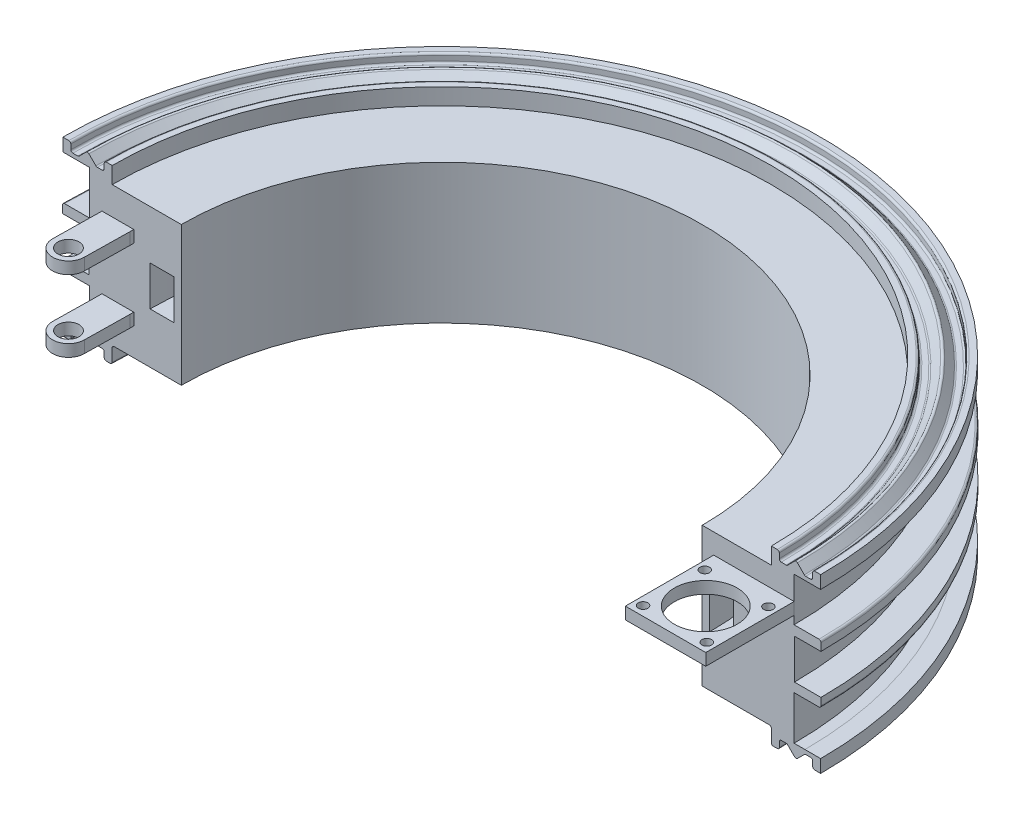
SolidWorks part; units mm, degrees
ref_plane "Front Plane" through (0, 0, 0) normal (0, 0, 1) x (1, 0, 0)
ref_plane "Top Plane" through (0, 0, 0) normal (0, 1, 0) x (1, 0, 0)
ref_plane "Right Plane" through (0, 0, 0) normal (1, 0, 0) x (0, 0, -1)
sketch "Sketch1" plane through (0, 0, 0) normal (0, 0, 1) x (1, 0, 0)
  line L0 (0, 21.2431) -> (0, -20.7935) construction
  line L1 (0, 21.2431) -> (0, -13.7569)
  line L12 (-23.1796, -1.3005) -> (-23.1796, 8.6995)
  line L14 (-29.847, 8.6995) -> (-29.847, 11.1239)
  line L23 (0, 3.7431) -> (-36.1577, 3.7431) construction
  line L25 (-7.8424, 8.9508) -> (-1.8424, 8.9508)
  line L26 (-7.8424, 8.9508) -> (-7.8424, -1.0492)
  line L27 (-7.8424, -1.0492) -> (-1.8424, -1.0492)
  line L28 (-1.8424, 8.9508) -> (-1.8424, -1.0492)
  line L29 (-21.3184, 23.1426) -> (-23.5684, 25.3926)
  line L30 (-23.5684, 25.3926) -> (-25.8184, 23.1426)
  line L32 (-25.8184, 22.1426) -> (-23.0909, 22.1426)
  line L33 (-23.0909, 22.1426) -> (-23.0909, 11.1239)
  line L34 (-23.0909, 11.1239) -> (-29.847, 11.1239)
  line L35 (-29.847, -3.6377) -> (-23.0909, -3.6377)
  line L42 (-29.847, -3.6377) -> (-29.847, -1.3005)
  line L43 (-29.847, -1.3005) -> (-23.1796, -1.3005)
  line L44 (-29.847, 8.6995) -> (-23.1796, 8.6995)
  line L45 (-21.3184, 23.1426) -> (-19.3684, 23.1426)
  line L46 (-19.3684, 23.1426) -> (-19.3684, 25.4025)
  line L47 (-17.3684, 25.4025) -> (-17.3684, 21.2431)
  line L48 (-17.3684, 21.2431) -> (0, 21.2431)
  line L49 (-19.3684, 25.4025) -> (-17.3684, 25.4025)
  line L50 (-25.8184, 23.1426) -> (-27.7684, 23.1426)
  line L51 (-27.7684, 23.1426) -> (-27.7684, 25.3862)
  line L52 (-27.7684, 25.3862) -> (-29.7684, 25.3862)
  line L53 (-29.7684, 25.3862) -> (-29.7684, 22.1426)
  line L54 (-29.7684, 22.1426) -> (-25.8184, 22.1426)
  line L65 (-29.7684, -14.6564) -> (-25.8184, -14.6564)
  line L66 (-29.7684, -17.9) -> (-29.7684, -14.6564)
  line L67 (-27.7684, -17.9) -> (-29.7684, -17.9)
  line L68 (-27.7684, -15.6564) -> (-27.7684, -17.9)
  line L69 (-25.8184, -15.6564) -> (-27.7684, -15.6564)
  line L70 (-19.3684, -17.9163) -> (-17.3684, -17.9163)
  line L71 (-17.3684, -13.7569) -> (0, -13.7569)
  line L72 (-17.3684, -17.9163) -> (-17.3684, -13.7569)
  line L73 (-19.3684, -15.6564) -> (-19.3684, -17.9163)
  line L74 (-21.3184, -15.6564) -> (-19.3684, -15.6564)
  line L75 (-23.0909, -14.6564) -> (-23.0909, -3.6377)
  line L76 (-25.8184, -14.6564) -> (-23.0909, -14.6564)
  line L77 (-23.5684, -17.9064) -> (-25.8184, -15.6564)
  line L78 (-21.3184, -15.6564) -> (-23.5684, -17.9064)
  line L79 (-29.847, 8.6995) -> (-29.847, -5.9646) construction
  line L80 (-23.5684, 25.3926) -> (-40.3715, 25.3926) construction
  line L81 (-40.3715, 25.3926) -> (-10.8825, 25.3926) construction
  line L82 (-23.0909, 11.1239) -> (-23.0909, -3.6377) construction
  dimension "D1" = 35
  dimension "D2" = 1.95
  dimension "D3" = 1
  dimension "D4" = 4.5
  dimension "D6" = 2
  dimension "D7" = 2
  dimension "D8" = 10
  dimension "D10" = 10
  dimension "D11" = 6
sketch "Sketch3" plane through (0, 0, 0) normal (0, 1, 0) x (1, 0, 0)
  arc A0 (0, 0) -> (130.92, 0) centre (65.46, 0) cw
sweep "Sweep3" add profiles "Sketch1" path "Sketch3"
sketch "Sketch13" plane through (0, 0, 0) normal (0, 0, 1) x (1, 0, 0)
  line L4 (-7.8424, 3.9508) -> (-7.8424, 18.9333) construction
  line L5 (-7.8424, -1.0492) -> (-7.8424, 8.9508) construction
  line L6 (-7.8424, 18.9333) -> (-7.8424, -5.0069) construction
  line L7 (-23.1796, 3.6995) -> (-1.1121, 3.6995) construction
  line L8 (-23.1796, 8.6995) -> (-23.1796, -1.3005) construction
  line L9 (-16.2449, 7.1426) -> (-16.2449, 2.1426) construction
  line L15 (-19.9387, -3.8005) -> (-11.9387, -3.8005)
  line L16 (-11.9387, -3.8005) -> (-11.9387, -6.8005)
  line L22 (-11.9387, -6.8005) -> (-19.9387, -6.8005)
  line L23 (-19.9387, -6.8005) -> (-19.9387, -3.8005)
  line L24 (-19.9387, 11.1995) -> (-11.9387, 11.1995)
  line L25 (-19.9387, 14.1995) -> (-19.9387, 11.1995)
  line L26 (-11.9387, 14.1995) -> (-19.9387, 14.1995)
  line L27 (-11.9387, 11.1995) -> (-11.9387, 14.1995)
  dimension "D1" = 3
  dimension "D2" = 8
  dimension "D3" = 7.5
ref_plane "Plane3" through (0, 3.6995, 0) normal (0, 1, 0) x (1, 0, 0)
sketch "Sketch17" plane through (0, 0, 0) normal (0, 0, 1) x (1, 0, 0)
  line L15 (154.0109, 16.1931) -> (133.8109, 16.1931)
  line L16 (154.0109, 22.1426) -> (154.0109, 11.1239) construction
  line L17 (133.8109, 16.1931) -> (133.8109, 13.1931)
  line L18 (133.8109, 13.1931) -> (154.0109, 13.1931)
  line L19 (154.0109, 13.1931) -> (154.0109, 16.1931)
  line L20 (130.92, 21.2431) -> (148.2883, 21.2431) construction
  dimension "D1" = 5.05
  dimension "D2" = 3
  dimension "D3" = 20.2
fillet "Fillet1" radius 0.5 1 edges at (65.46, 25.3926, -89.0284)
fillet "Fillet2" radius 0.5 1 edges at (65.46, 23.1426, -91.2784)
fillet "Fillet3" radius 0.5 1 edges at (65.46, 23.1426, -93.2284)
fillet "Fillet4" radius 0.5 2 edges at (65.46, 23.1426, -84.8284) (65.46, 23.1426, -86.7784)
fillet "Fillet5" radius 0.5 3 edges at (65.46, -17.9163, -84.8284) (65.46, -15.6564, -86.7784) (65.46, -17.9064, -89.0284)
fillet "Fillet6" radius 0.5 3 edges at (65.46, -13.7569, -82.8284) (65.46, -17.9163, -82.8284) (65.46, -15.6564, -84.8284)
fillet "Fillet7" radius 0.5 3 edges at (65.46, -15.6564, -91.2784) (65.46, -17.9, -93.2284) (65.46, -15.6564, -93.2284)
fillet "Fillet9" radius 0.5 2 edges at (65.46, -3.6377, -95.3069) (65.46, 11.1239, -95.3069)
fillet "Fillet10" radius 0.5 2 edges at (65.46, 25.3862, -93.2284) (65.46, 25.4025, -84.8284)
extrude "Boss-Extrude6" add sketch "Sketch13" along normal blind 1
sketch "Sketch19" plane through (0, 14.1995, 0) normal (0, 1, 0) x (1, 0, 0)
  line L0 (-19.9387, -1) -> (-20.1153, -12.2376)
  line L1 (-11.9387, -1) -> (-12.1153, -12.2376)
  circle A0 centre (-16.1153, -12.2376) radius 2.65
  circle A1 centre (-16.1153, -12.2376) radius 4
  line M5 (-19.9387, -1) -> (-11.9387, -1)
  dimension "D1" = 5.3
extrude "Boss-Extrude7" add sketch "Sketch19" against normal blind 3 contours A1 L1 L0 M5 | L1 A1 A0 region at (-15.9928, 14.1995, 5.0972) region at (-16.0543, 14.1995, 8.3512)
mirror "Mirror1" about plane through (0, 3.6995, 0) normal (0, 1, 0) of "Boss-Extrude6", "Boss-Extrude7"
extrude "Boss-Extrude8" add sketch "Sketch17" along normal blind 22.2 contours L15 L17 L18 L19
sketch "Sketch21" plane through (0, 13.1931, 0) normal (0, -1, 0) x (1, 0, 0)
  line L0 (133.8109, 22.2) -> (154.0109, 22.2) construction
  line L1 (133.8109, 22.2) -> (133.8109, 0) construction
  line L3 (143.9109, 12.1) -> (130.587, 12.1) construction
  line L4 (130.587, 12.1) -> (159.1422, 12.1) construction
  line L5 (143.9109, 12.1) -> (143.9109, 26.1323) construction
  line L6 (143.9109, 26.1323) -> (143.9109, -1.5088) construction
  circle A0 centre (143.9109, 12.1) radius 7.9
  circle A1 centre (135.9085, 19.85) radius 1.2
  circle A2 centre (135.9085, 4.35) radius 1.2
  circle A3 centre (151.9132, 4.35) radius 1.2
  circle A4 centre (151.9132, 19.85) radius 1.2
  dimension "D1" = 10.1
  dimension "D3" = 11.14
  dimension "D2" = 10.1
  dimension "D4" = 2.35
extrude "Cut-Extrude3" cut sketch "Sketch21" against normal blind 22.2
